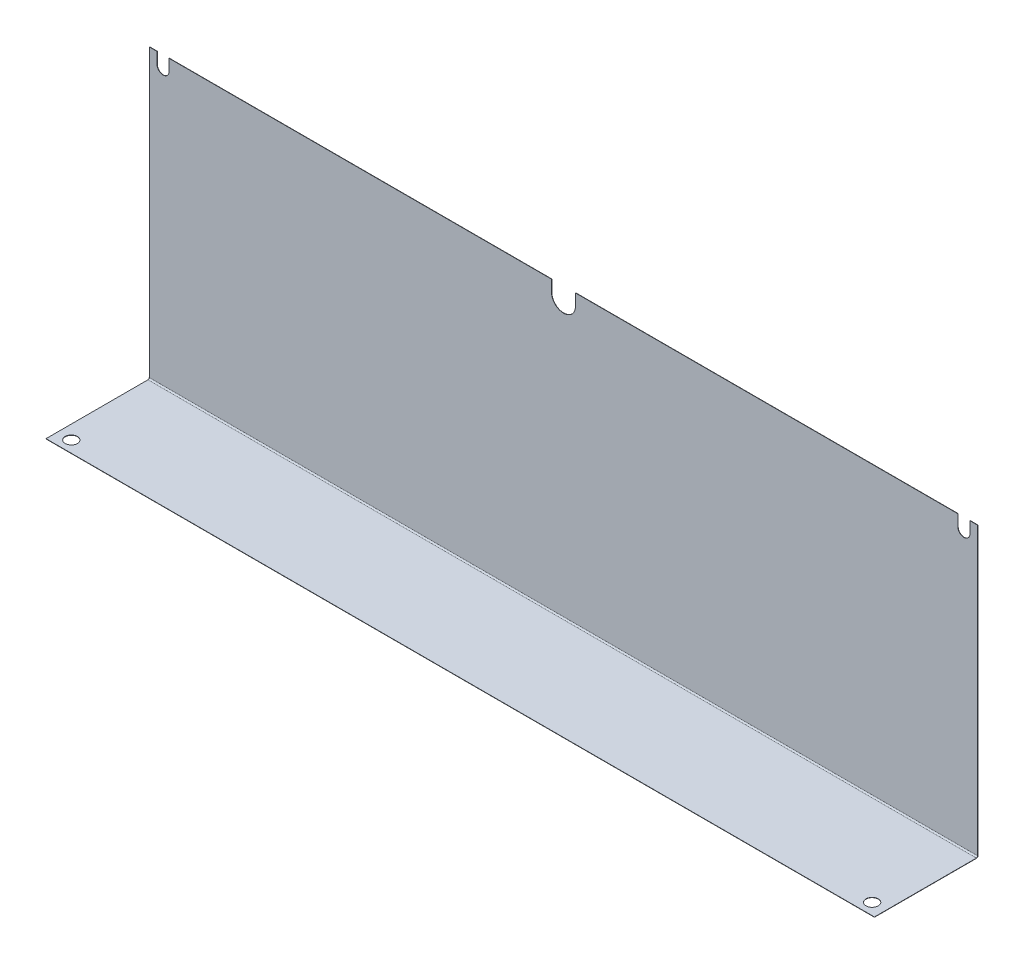
SolidWorks part; units mm, degrees
note: The reader was unsure of these and kept them because the rebuilt part matched: thickness of "Base-Flange1", "Edge-Flange1", "Sheet-Metal(1)", "Sheet-Metal(2)", "Sheet-Metal(3)", "Sheet-Metal(4)", "Sheet-Metal(5)", "Sheet-Metal(6)"; flange length of "Edge-Flange1".
ref_plane "Front Plane" through (0, 0, 0) normal (0, 0, 1) x (1, 0, 0)
ref_plane "Top Plane" through (0, 0, 0) normal (0, 1, 0) x (1, 0, 0)
ref_plane "Right Plane" through (0, 0, 0) normal (1, 0, 0) x (0, 0, -1)
sketch "Sketch1" plane through (0, 0, 0) normal (0, 1, 0) x (1, 0, 0)
  line L1 (0, 0) -> (457.2, 0)
  line L2 (0, 0) -> (0, 57.15)
  line L3 (0, 57.15) -> (457.2, 57.15)
  line L4 (457.2, 0) -> (457.2, 57.15)
  dimension "D1" = 457.2
  dimension "D2" = 57.15
base flange "Base-Flange1" sketch "Sketch1" thickness 0.1588 reverse thickness direction no parameters "D1"=0.7366
edge flange "Edge-Flange1" sketch "Sketch8" flange angle 90 flange length 158.75 flange position material inside bend radius 0.7366 thickness 0.1588 relief rectangular parameters "D6"=10
sketch "Sketch8" plane through (0, 0, -57.15) normal (0, 0, -1) x (-1, 0, 0)
  line L0 (-457.2, 0) -> (0, 0) construction
  line L1 (-457.2, 0) -> (0, 0)
  line L2 (-457.2, 0) -> (-457.2, 158.75)
  line L3 (-457.2, 158.75) -> (0, 158.75)
  line L4 (0, 158.75) -> (0, 0)
  dimension "D1" = 158.75
bend "EdgeBend1" bend radius 0.7366 bend angle 90 parameters "D5"=1
sketch "Sketch9" plane through (0, 0, -57.15) normal (0, 0, -1) x (-1, 0, 0)
  line L0 (-446.278, 152.4) -> (-446.278, 158.75)
  line L1 (0, 158.75) -> (-457.2, 158.75) construction
  line L2 (-452.882, 152.4) -> (-452.882, 158.75)
  line L3 (-228.6, 158.75) -> (-228.6, 143.1331) construction
  line L4 (-457.2, 158.75) -> (-457.2, 0.7366) construction
  line L5 (-452.882, 158.75) -> (-446.278, 158.75)
  line L6 (-10.922, 152.4) -> (-10.922, 158.75)
  line L7 (-10.922, 158.75) -> (-4.318, 158.75)
  line L8 (-4.318, 158.75) -> (-4.318, 152.4)
  line L9 (0, 0.7366) -> (0, 158.75) construction
  line L10 (-235.204, 152.4) -> (-235.204, 158.75)
  line L11 (-235.204, 158.75) -> (-221.996, 158.75)
  line L12 (-221.996, 158.75) -> (-221.996, 152.4)
  arc A0 (-452.882, 152.4) -> (-446.278, 152.4) centre (-449.58, 152.4) ccw
  arc A1 (-10.922, 152.4) -> (-4.318, 152.4) centre (-7.62, 152.4) ccw
  arc A2 (-221.996, 152.4) -> (-235.204, 152.4) centre (-228.6, 152.4) cw
  dimension "D1" = 6.604
  dimension "D4" = 6.604
  dimension "D7" = 6.604
  dimension "D2" = 6.35
  dimension "D3" = 7.62
  dimension "D5" = 6.35
  dimension "D6" = 7.62
  dimension "D8" = 6.35
extrude "Cut-Extrude1" cut sketch "Sketch9" against normal through all normal cut yes
sketch "Sketch10" plane through (0, 0, 0) normal (0, 0, 1) x (1, 0, 0)
  line L0 (0, -0.1588) -> (457.2, -0.1588) construction
  line L1 (457.2, 0) -> (431.8, 0)
  line L2 (457.2, 0) -> (457.2, -0.1588)
  line L3 (457.2, -0.1588) -> (431.8, -0.1588)
  line L4 (431.8, 0) -> (431.8, -0.1588)
  line L6 (0, 0) -> (25.4, 0)
  line L7 (0, 0) -> (0, -0.1588)
  line L8 (0, -0.1588) -> (25.4, -0.1588)
  line L9 (25.4, 0) -> (25.4, -0.1588)
  dimension "D1" = 25.4
  dimension "D2" = 25.4
extrude "Boss-Extrude1" [suppressed] add sketch "Sketch10" along normal blind 25.4
hole_wizard "1/4 Clearance Hole1" [suppressed] positions "3DSketch1" profile "Sketch11" hole size "1/4" standard "ANSI Inch"
sketch3d "3DSketch1" [suppressed]
  line L0 (457.2, -0.1588, 25.4) -> (457.2, -0.1588, -49.9046) construction
  line L1 (431.8, -0.1588, 25.4) -> (457.2, -0.1588, 25.4) construction
  line L2 (25.4, -0.1588, 25.4) -> (25.4, -0.1588, 0) construction
  line L3 (0, -0.1588, 25.4) -> (25.4, -0.1588, 25.4) construction
  point P0 (12.7, -0.1588, 12.7)
  point P2 (444.5, -0.1588, 12.7)
  dimension "D1" = 12.7
  dimension "D2" = 12.7
  dimension "D3" = 12.7
  dimension "D4" = 12.7
sketch "Sketch11" plane through (12.7, -0.1588, 12.7) normal (1, 0, 0) x (0, 0, -1)
  line L0 (0, 0) -> (0, 27.4298)
  line L1 (0, 27.4298) -> (3.3782, 25.4)
  line L2 (3.3782, 25.4) -> (3.3782, 0)
  line L5 (3.3782, 0) -> (0, 0)
  line L10 (0, 27.4298) -> (-3.3782, 25.4) construction
  line L11 (0, -6.35) -> (0, 107.95) construction
  dimension "Hole Dia." = 6.7564
  dimension "Hole Depth" = 25.4
  dimension "Drill Angle" = 118
hole_wizard "1/4 Clearance Hole2" positions "3DSketch3" profile "Sketch13" hole size "1/4" standard "ANSI Inch"
sketch3d "3DSketch3"
  line L0 (0, -0.1587, -56.2547) -> (0, -0.1588, 0) construction
  line L1 (0, -0.1588, 0) -> (457.2, -0.1588, 0) construction
  line L2 (457.2, -0.1588, 0) -> (457.2, -0.1588, -56.2547) construction
  point P0 (7.62, -0.1588, -6.35)
  point P2 (449.58, -0.1588, -6.35)
  dimension "D1" = 7.62
  dimension "D2" = 6.35
  dimension "D3" = 7.62
  dimension "D4" = 6.35
sketch "Sketch13" plane through (7.62, -0.1588, -6.35) normal (1, 0, 0) x (0, 0, -1)
  line L0 (0, 0) -> (0, 27.4298)
  line L1 (0, 27.4298) -> (3.3782, 25.4)
  line L2 (3.3782, 25.4) -> (3.3782, 0)
  line L5 (3.3782, 0) -> (0, 0)
  line L10 (0, 27.4298) -> (-3.3782, 25.4) construction
  line L11 (0, -6.35) -> (0, 107.95) construction
  dimension "Hole Dia." = 6.7564
  dimension "Hole Depth" = 25.4
  dimension "Drill Angle" = 118
sketch "Bend-Lines1" plane through (0, 0, 0) normal (0, 1, 0) x (1, 0, 0)
sketch "Bounding-Box1" plane through (0, 0, 0) normal (0, 1, 0) x (1, 0, 0)
sheet metal parameters "Sheet-Metal(1)" thickness 0.1588 parameters "D1"=0.7366
flat pattern "Flat-Pattern(1)" [suppressed]
sketch "Bend-Lines2" plane through (0, 0, 0) normal (0, 1, 0) x (1, 0, 0)
sketch "Bounding-Box2" [suppressed] plane through (0, 0, 0) normal (0, 1, 0) x (1, 0, 0)
sheet metal parameters "Sheet-Metal(2)" thickness 0.1588 parameters "D1"=0.7366, "D7"=3.175
flat pattern "Flat-Pattern(1)" [suppressed]
sketch "Bend-Lines2" plane through (0, 0, 0) normal (0, 1, 0) x (1, 0, 0)
sketch "Bounding-Box2" [suppressed] plane through (0, 0, 0) normal (0, 1, 0) x (1, 0, 0)
bend of the flat pattern "Flatten-<EdgeBend1>1"
sheet metal parameters "Sheet-Metal(3)" thickness 0.1588 parameters "D1"=0.7366, "D7"=3.175
flat pattern "Flat-Pattern(1)" [suppressed]
sketch "Bend-Lines2" plane through (0, 0, 0) normal (0, 1, 0) x (1, 0, 0)
sketch "Bounding-Box2" [suppressed] plane through (0, 0, 0) normal (0, 1, 0) x (1, 0, 0)
bend of the flat pattern "Flatten-<EdgeBend1>1"
sheet metal parameters "Sheet-Metal(4)" thickness 0.1588 parameters "D1"=0.7366, "D7"=3.175
flat pattern "Flat-Pattern(1)" [suppressed]
sketch "Bend-Lines2" plane through (0, 0, 0) normal (0, 1, 0) x (1, 0, 0)
sketch "Bounding-Box2" [suppressed] plane through (0, 0, 0) normal (0, 1, 0) x (1, 0, 0)
bend of the flat pattern "Flatten-<EdgeBend1>1"
sheet metal parameters "Sheet-Metal(5)" thickness 0.1588 parameters "D1"=0.7366, "D7"=3.175
flat pattern "Flat-Pattern(1)" [suppressed]
sketch "Bend-Lines2" plane through (0, 0, 0) normal (0, 1, 0) x (1, 0, 0)
sketch "Bounding-Box2" [suppressed] plane through (0, 0, 0) normal (0, 1, 0) x (1, 0, 0)
bend of the flat pattern "Flatten-<EdgeBend1>1"
sheet metal parameters "Sheet-Metal(6)" thickness 0.1588 parameters "D1"=0.7366, "D7"=3.175
flat pattern "Flat-Pattern(1)" [suppressed]
sketch "Bend-Lines2" plane through (0, 0, 0) normal (0, 1, 0) x (1, 0, 0)
sketch "Bounding-Box2" [suppressed] plane through (0, 0, 0) normal (0, 1, 0) x (1, 0, 0)
bend of the flat pattern "Flatten-<EdgeBend1>1"
